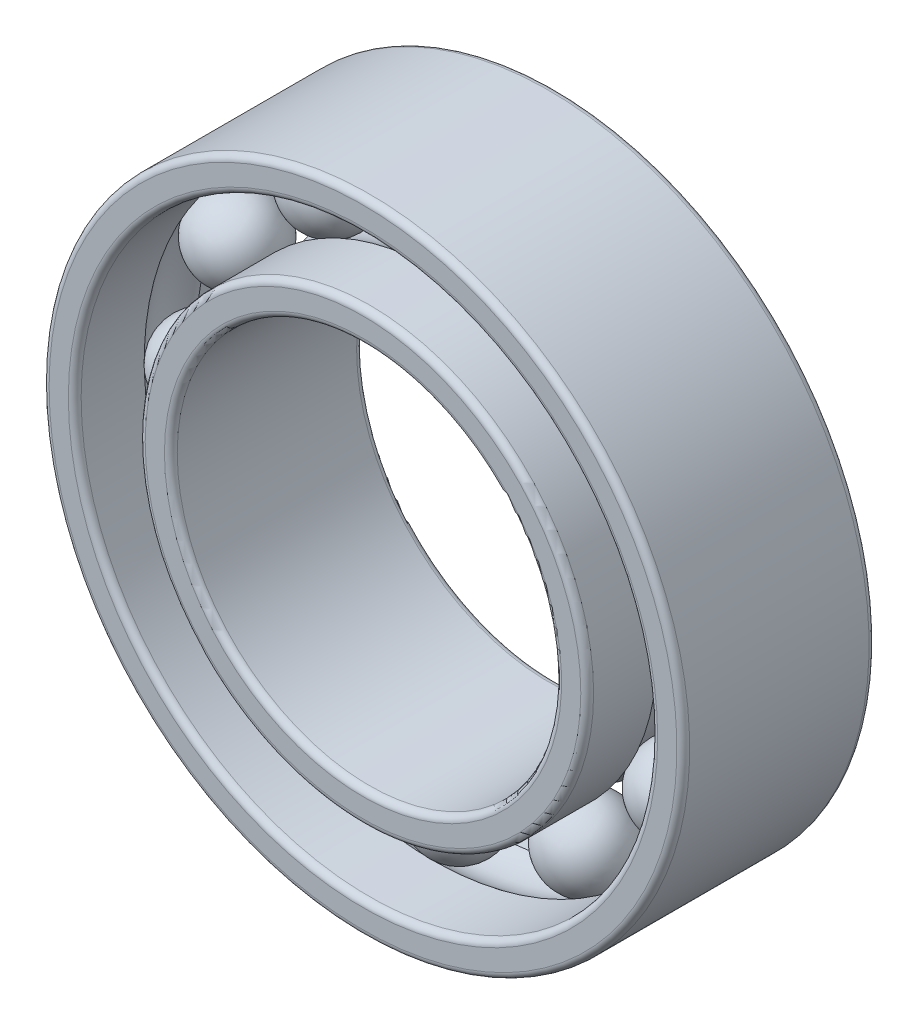
SolidWorks part; units mm, degrees
material "Legierter Stahl"
ref_plane "Ebene vorne" through (0, 0, 0) normal (0, 0, 1) x (1, 0, 0)
ref_plane "Ebene oben" through (0, 0, 0) normal (0, 1, 0) x (1, 0, 0)
ref_plane "Ebene rechts" through (0, 0, 0) normal (1, 0, 0) x (0, 0, -1)
sketch "Skizze1" plane through (0, 0, 0) normal (1, 0, 0) x (0, 0, -1)
  line L0 (0, 0) -> (32.8284, 0) construction
  line L1 (0, 0) -> (0, 22.1569) construction
  line L2 (-1.5, 5) -> (1.5, 5)
  line L3 (1.5, 5) -> (1.5, 4.5)
  line L4 (1.5, 4.5) -> (0.4153, 4.5)
  line L5 (0.4153, 3.5) -> (1.5, 3.5)
  line L6 (1.5, 3.5) -> (1.5, 3)
  line L7 (1.5, 3) -> (-1.5, 3)
  line L8 (-1.5, 3.5) -> (-1.5, 3)
  line L9 (-0.4153, 3.5) -> (-1.5, 3.5)
  line L10 (-1.5, 4.5) -> (-0.4153, 4.5)
  line L11 (-1.5, 5) -> (-1.5, 4.5)
  line L12 (-0.4153, 4.5) -> (0, 4) construction
  line L13 (0, 4) -> (0.4153, 3.5) construction
  line L14 (-0.65, 4) -> (0.65, 4)
  circle A0 centre (0, 4) radius 0.65
  point P17 (0, 3)
  point P22 (0, 5)
  dimension "D1" = 6
  dimension "D6" = 1.3
  dimension "D2" = 10
  dimension "D3" = 3
  dimension "D4" = 7
  dimension "D5" = 9
revolve "Rotation1" add sketch "Skizze1" angle 360 about L0 region at (0, 4.7614, 0) region at (0, 3.2386, 0)
revolve "Rotation3" add sketch "Skizze1<5>" angle 360 about L14 region at (0, 4.2759, 0)
sketch "Skizze1<5>" plane through (0, 0, 0) normal (1, 0, 0) x (0, 0, -1) same geometry as "Skizze1"
ref_axis "Achse1" through (0, 0, -1.5) along (0, 0, 1)
pattern_circular "Kreismuster4" count 12 over 360 about axis through (0, 0, -1.5) along (0, 0, 1) of bodies 110
fillet "Verrundung1" radius 0.1 4 edges at (4.5, 0, -1.5) (4.5, 0, 1.5) (5, 0, -1.5) (5, 0, 1.5)
fillet "Verrundung2" radius 0.1 4 edges at (3.5, 0, -1.5) (3, 0, -1.5) (3.5, 0, 1.5) (3, 0, 1.5)
